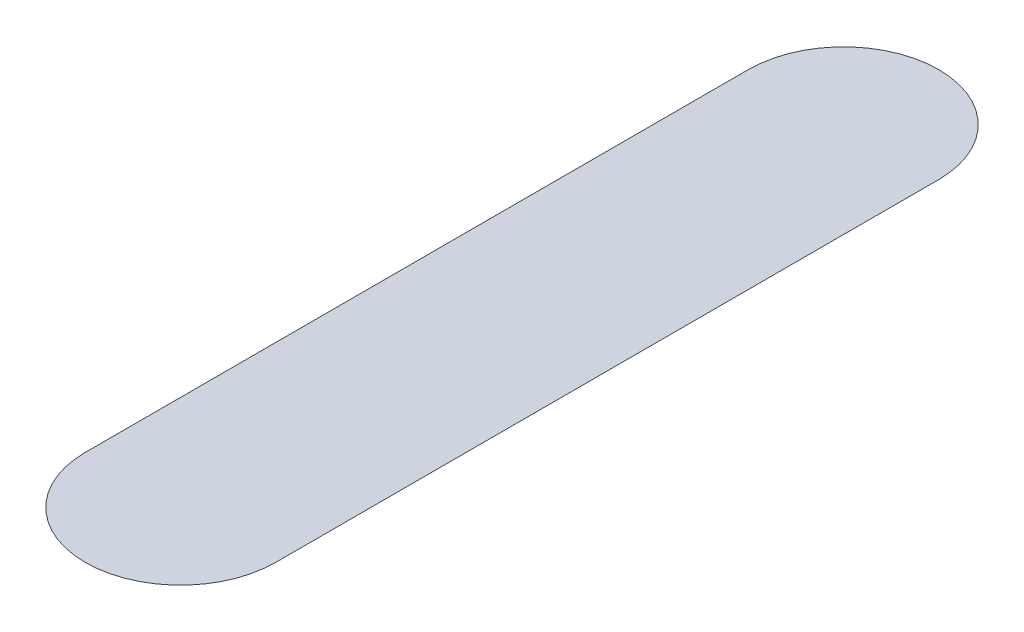
SolidWorks part; units mm, degrees
ref_plane "Plane1" through (0, 0, 0) normal (0, 0, 1) x (1, 0, 0)
ref_plane "Plane2" through (0, 0, 0) normal (0, 1, 0) x (1, 0, 0)
ref_plane "Plane3" through (0, 0, 0) normal (1, 0, 0) x (0, 0, -1)
sketch "Sketch1" plane through (0, 0, 0) normal (0, 0, 1) x (1, 0, 0)
  line L0 (-25, 5) -> (25, 5)
  line L1 (-25, 5) -> (-25, 0)
  line L2 (25, 0) -> (-25, 0)
  line L3 (25, 0) -> (25, 5)
  line L4 (0, 5) -> (0, 0) construction
  line L5 (50, 0) -> (-50, 0) construction
  dimension "D1" = 50
  dimension "D2" = 5
extrude "Base-Extrude" add sketch "Sketch1" along normal mid plane 140
sketch "Sketch10" plane through (0, 0, 0) normal (0, 1, 0) x (-1, 0, 0)
  line L4 (10, 40) -> (10, -40) construction
  line L5 (0, 50) -> (0, -50) construction
  line L6 (-10, 40) -> (-10, -40) construction
  line L8 (-10, 0) -> (10, 0) construction
  arc A0 (10, -40) -> (-10, -40) centre (0, -40) cw construction
  arc A1 (-10, 40) -> (10, 40) centre (0, 40) cw construction
  dimension "Rib Length" = 100
  dimension "Rib Width" = 20
ref_plane "Plane4" through (0, 0, -40) normal (0, 0, 1) x (1, 0, 0)
ref_plane "Plane5" through (0, 0, 40) normal (0, 0, 1) x (1, 0, 0)
sketch "Sketch2" plane through (0, 0, -40) normal (0, 0, 1) x (1, 0, 0)
  line L0 (25, 0) -> (-25, 0) construction
  line L1 (0, -50) -> (0, 50) construction
  line L2 (10, 0) -> (-10, 0)
  arc A0 (-10, 0) -> (10, 0) centre (0, 10.5) ccw
  dimension "Height" = 4
extrude "Boss-Extrude1" add sketch "Sketch2" along normal up to surface (80 mm away) up to plane "Plane5"
sketch "Sketch7" plane through (0, 0, 40) normal (0, 0, 1) x (1, 0, 0)
  line L0 (0, 0.9975) -> (0, -6.5364) construction
  line L1 (0, 0) -> (0, -4)
  line L2 (10, 0) -> (-10, 0)
  line L3 (0, 0) -> (-10, 0)
  arc A1 (-10, 0) -> (10, 0) centre (0, 10.5) ccw
  arc A2 (-10, 0) -> (0, -4) centre (0, 10.5) ccw
  dimension "D1" = 0
revolve "Boss-Revolve3" add sketch "Sketch7" angle 180 about L0 reverse direction yes
sketch "Sketch9" plane through (0, 0, -40) normal (0, 0, 1) x (1, 0, 0)
  line L0 (0, 0.9975) -> (0, -6.5364) construction
  line L1 (0, 0) -> (0, -4)
  line L2 (10, 0) -> (-10, 0) construction
  line L3 (0, 0) -> (-10, 0)
  arc A2 (-10, 0) -> (0, -4) centre (0, 10.5) ccw
revolve "Boss-Revolve4" add sketch "Sketch9" angle 180 about L0
fillet "Fillet3" radius 4 4 edges at (10, 0, 0) (0, 0, 50) (0, 0, -50) (-10, 0, 0)
sketch "Sketch3" plane through (-25, 0, 0) normal (-1, 0, 0) x (0, 0, 1)
  line L4 (-70, 0) -> (70, 0)
  line L5 (70, 0) -> (70, 5)
  line L6 (70, 5) -> (-70, 5)
  line L7 (-70, 5) -> (-70, 0)
  line L8 (-70, 0) -> (70, 0)
  line L9 (70, 0) -> (70, 5)
  line L10 (70, 5) -> (-70, 5)
  line L11 (-70, 5) -> (-70, 0)
  dimension "D1" = 0
extrude "Cut-Extrude1" cut sketch "Sketch3" against normal through all
sketch "Orientation Sketch" plane through (0, 0, 0) normal (0, 1, 0) x (-1, 0, 0)
  line L2 (11.4891, -40) -> (11.4891, 40)
  line L3 (-11.4891, 40) -> (-11.4891, -40)
  line L4 (11.4891, -40) -> (11.4891, 40)
  line L5 (-11.4891, 40) -> (-11.4891, -40)
  arc A2 (11.4891, 40) -> (-11.4891, 40) centre (0, 40) ccw
  arc A3 (-11.4891, -40) -> (11.4891, -40) centre (0, -40) ccw
  arc A4 (11.4891, 40) -> (-11.4891, 40) centre (0, 40) ccw
  arc A5 (-11.4891, -40) -> (11.4891, -40) centre (0, -40) ccw
  dimension "D1" = 0
